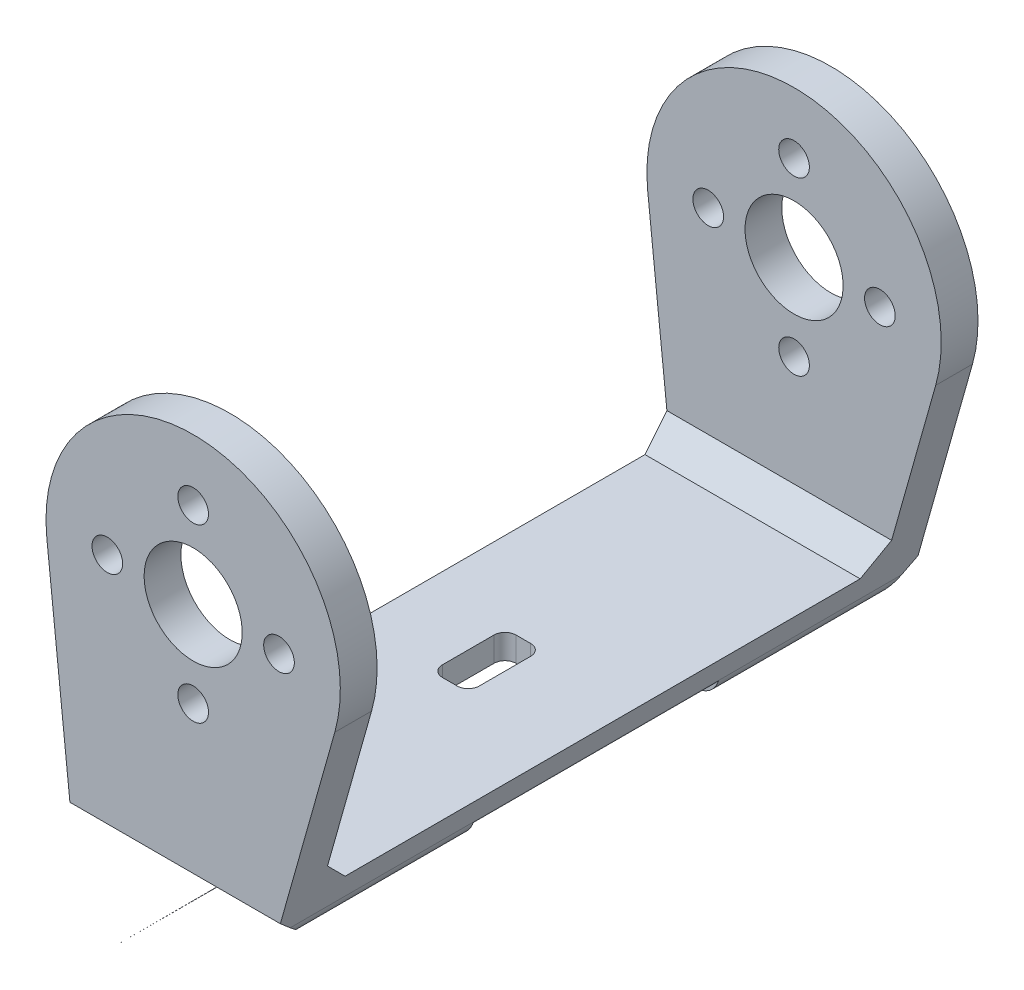
SolidWorks part; units mm, degrees
ref_plane "Спереди" through (0, 0, 0) normal (0, 0, 1) x (1, 0, 0)
ref_plane "Сверху" through (0, 0, 0) normal (0, 1, 0) x (1, 0, 0)
ref_plane "Справа" through (0, 0, 0) normal (1, 0, 0) x (0, 0, -1)
sketch "Эскиз1" plane through (0, 0, 0) normal (0, 0, 1) x (1, 0, 0)
  line L0 (0, 2) -> (56.5685, 58.5685) construction
  line L1 (4.5709, -21.5) -> (2.2093, 0.7321)
  line L2 (70.7107, 44.4264) -> (14.1421, -12.1421) construction
  line L3 (14.1421, -12.1421) -> (0, 2) construction
  line L4 (20.9819, -17.9572) -> (25.6921, -1.2579)
  line L5 (8.0709, -18) -> (18.0709, -18) construction
  line L6 (20.5709, -18) -> (20.5709, -21.5) construction
  line L7 (20.5709, -21.5) -> (16.5419, -21.5) construction
  line L8 (18.0709, -18) -> (18.0709, -19) construction
  line L9 (16.7822, -19.4143) -> (19.057, -19.4143)
  line L10 (14.1424, 1.9997) -> (14.1424, 8.9997) construction
  line L17 (17.0709, -20) -> (16.7822, -20) construction
  circle A0 centre (14.1424, 1.9997) radius 4
  circle A1 centre (14.1424, 1.9997) radius 18 construction
  arc A2 (4.5709, -21.5) -> (11.2516, -22.9605) centre (8.0709, -21.5) ccw
  arc A3 (12.1987, -28.5401) -> (16.7822, -20) centre (16.7822, -25.5) cw construction
  circle A4 centre (8.0709, -21.5) radius 1.25
  arc A5 (18.0709, -19) -> (17.0709, -20) centre (17.0709, -19) cw construction
  arc A6 (17.0044, -20.4985) -> (18.189, -18) centre (17.0709, -19) ccw construction
  arc A7 (17.0044, -20.4985) -> (16.5152, -20.5007) centre (16.7822, -25.5) ccw
  arc A8 (6.2308, -24.4772) -> (7.6172, -25.7507) centre (3.602, -28.7304) cw construction
  arc A9 (16.5152, -20.5007) -> (16.5419, -21.5) centre (16.5419, -21) ccw construction
  arc A10 (16.7822, -19.4143) -> (11.2516, -22.9605) centre (16.7822, -25.5) ccw
  arc A11 (19.057, -19.4143) -> (20.9819, -17.9572) centre (19.057, -17.4143) ccw
  circle A12 centre (14.1424, 8.9997) radius 1.25
  circle A13 centre (21.1424, 1.9997) radius 1.25
  circle A14 centre (14.1424, -5.0003) radius 1.25
  circle A15 centre (7.1424, 1.9997) radius 1.25
  arc A16 (25.6921, -1.2579) -> (2.3806, -0.3806) centre (14.1424, 1.9997) ccw
  point P38 (20.5709, -19.4143)
  point P45 (14.1424, 1.9997)
  point P46 (20.5709, -19.4143)
  dimension "D1" = 0.5
  dimension "D2" = 5.5
  dimension "D3" = 1
  dimension "D4" = 4
  dimension "D5" = 2
  dimension "D6" = 5
  dimension "D7" = 19.9997
extrude "Бобышка-Вытянуть1" add sketch "Эскиз1" along normal blind 52 contours L4 A16 L1 A2 A10 L9 A11 A0 A4 A12 A13 A14 A15 region at (3.8455, -10.3356, 0)
sketch "Эскиз2" plane through (0, 0, 0) normal (1, 0, 0) x (0, 0, -1)
  line L0 (0, 14) -> (-3, 14)
  line L1 (0, 14) -> (-52, 14) construction
  line L2 (-3, 14) -> (-3, -14)
  line L3 (-5, -16) -> (-47, -16)
  line L4 (-49, -14) -> (-49, 14)
  line L5 (-49, 14) -> (-3, 14)
  line L6 (0, -21.5) -> (-52, -21.5) construction
  line L7 (-26, -21.5) -> (-26, -18) construction
  line L8 (-26, -18) -> (-36, -18)
  line L9 (-36, -18) -> (-36, -25)
  line L10 (-52, -25) -> (0, -25) construction
  line L11 (-36, -25) -> (-16, -25)
  line L12 (-16, -25) -> (-16, -18)
  line L13 (-16, -18) -> (-26, -18)
  line L14 (-43, -25) -> (-52, -25)
  line L15 (0, -25) -> (0, -17)
  line L16 (0, -22.9605) -> (0, -19.4143) construction
  line L17 (-52, -25) -> (-52, -17)
  line L18 (-9, -25) -> (0, -25)
  line L19 (0, -17) -> (-9, -25)
  line L20 (-52, -17.9572) -> (-52, -19.4143) construction
  line L21 (-52, -17) -> (-43, -25)
  line L22 (-49, -14) -> (-47, -16)
  line L23 (-3, -14) -> (-5, -16)
  line L24 (-5, -16) -> (-5.1944, -16.1242)
  arc A0 (-49, -14) -> (-47, -16) centre (-47, -14) ccw
  arc A1 (-5, -16) -> (-3, -14) centre (-5, -14) ccw
  arc A3 (-36, -21.6568) -> (-35.8761, -21.5) centre (-43, -16) ccw
  point P22 (-49, -16)
  dimension "D2" = 2
  dimension "D1" = 30
extrude "Вырез-Вытянуть2" cut sketch "Эскиз2" along normal through all contours L5 L4 L3 L2 | L12 L13 L8 L9 L11 | L18 | L14 region at (0, -0.9583, 26) region at (0, -21.5, 26) region at (0, -22.3333, 49) region at (0, -22.3333, 3)
sketch "Эскиз3" plane through (0, -18, 0) normal (0, -1, 0) x (1, 0, 0)
  line L0 (8.0709, 38.0959) -> (8.0709, 15.5596) construction
  line L4 (4.5709, 37.7657) -> (4.5709, 16) construction
  line L5 (4.5709, 46.9375) -> (4.5709, 36) construction
  line L6 (20.9693, 16) -> (4.1991, 16) construction
  line L7 (8.0709, 36) -> (8.0709, 16) construction
  line L8 (20.9693, 36) -> (4.1991, 36) construction
  line L9 (11.5709, 26) -> (16.5709, 26) construction
  line L10 (19.5709, 26) -> (20.9693, 26) construction
  line L11 (20.9693, 16) -> (20.9693, 36) construction
  line L12 (20.9693, 26) -> (20.9819, 28)
  line L13 (20.9819, 50.9231) -> (20.9819, 1.0769) construction
  line L14 (20.9819, 28) -> (17.0632, 28.9593)
  line L15 (20.9693, 26) -> (20.9693, 24)
  line L16 (20.9693, 24) -> (17.0632, 23.0407)
  circle A0 centre (8.0709, 26) radius 3.5 construction
  circle A1 centre (16.5709, 26) radius 3
  line M2 (20.9693, 16) -> (20.9693, 36)
extrude "Бобышка-Вытянуть3" add sketch "Эскиз3" along normal blind 1.5 contours L16 A1 L14 | A1 L16 L14 M2 region at (19.9517, -18, 26.0017) region at (16.5708, -18, 26)
chamfer "Фаска2" distance 1.5 distance2 2 1 edges at (20.9693, -19.5, 26.0015) first distance on face at (20.9693, -18.75, 26.0015)
sketch "Эскиз4" plane through (0, -18, 0) normal (0, -1, 0) x (-1, 0, 0)
  line L0 (-13.5709, -26) -> (-13.5709, -23.9)
  line L1 (-12.6709, -23) -> (-11.4709, -23)
  line L2 (-10.5709, -23.9) -> (-10.5709, -28.1)
  line L3 (-11.4709, -29) -> (-12.6709, -29)
  line L4 (-13.5709, -28.1) -> (-13.5709, -26)
  arc A0 (-17.0632, -28.9593) -> (-17.0632, -23.0407) centre (-16.5709, -26) ccw construction
  arc A1 (-11.4709, -29) -> (-10.5709, -28.1) centre (-11.4709, -28.1) ccw
  arc A2 (-12.6709, -29) -> (-13.5709, -28.1) centre (-12.6709, -28.1) cw
  arc A3 (-11.4709, -23) -> (-10.5709, -23.9) centre (-11.4709, -23.9) cw
  arc A4 (-12.6709, -23) -> (-13.5709, -23.9) centre (-12.6709, -23.9) ccw
  dimension "D1" = 0.9
  dimension "D2" = 3
extrude "Вырез-Вытянуть3" cut sketch "Эскиз4" against normal through all
ref_plane "Плоскость1" through (19.4696, -19.4696, 0) normal (0.7071, -0.7071, 0) x (-0.7071, -0.7071, 0)
sketch "Эскиз5" plane through (19.4696, -19.4696, 0) normal (0.7071, -0.7071, 0) x (-0.7071, -0.7071, 0)
  line L0 (8.2794, -16) -> (8.2794, -6.7056) construction
  line L1 (0.2526, -16) -> (0.2526, -2.7161) construction
  line L2 (8.2794, -11) -> (0.2526, -11) construction
  line L3 (-2.1388, -26) -> (19.8104, -26) construction
  line L4 (4.266, -7.5) -> (-0.734, -7.5)
  line L5 (8.2794, -41) -> (0.2526, -41) construction
  line L6 (0.2526, -36) -> (0.2526, -49.2839) construction
  line L7 (8.2794, -36) -> (8.2794, -45.2944) construction
  line L8 (-0.734, -14.5) -> (4.266, -14.5)
  line L9 (-0.734, -7.5) -> (-0.734, -14.5)
  line L10 (-0.734, -37.5) -> (4.266, -37.5)
  line L11 (-0.734, -44.5) -> (-0.734, -37.5)
  line L12 (4.266, -44.5) -> (-0.734, -44.5)
  circle A0 centre (4.266, -11) radius 3.5
  circle A1 centre (4.266, -41) radius 3.5
  dimension "D1" = 15
extrude "Бобышка-Вытянуть4" add sketch "Эскиз5" against normal up to surface (8.1728 mm away) from offset 1 contours A1 | A1 | A0 | A0 region at (19.0968, -19.8423, 11) region at (16.453, -22.4861, 11) region at (19.0968, -19.8423, 41) region at (16.453, -22.4861, 41) up to face at (12.0709, -16, 26) offset against normal yes
sketch "Эскиз6" plane through (18.7625, -18.7625, 0) normal (0.7071, -0.7071, 0) x (0, 0, -1)
  circle A0 centre (-11, -4.266) radius 1.25
  circle A1 centre (-41, -4.266) radius 1.25
extrude "Вырез-Вытянуть4" cut sketch "Эскиз6" against normal blind 5
